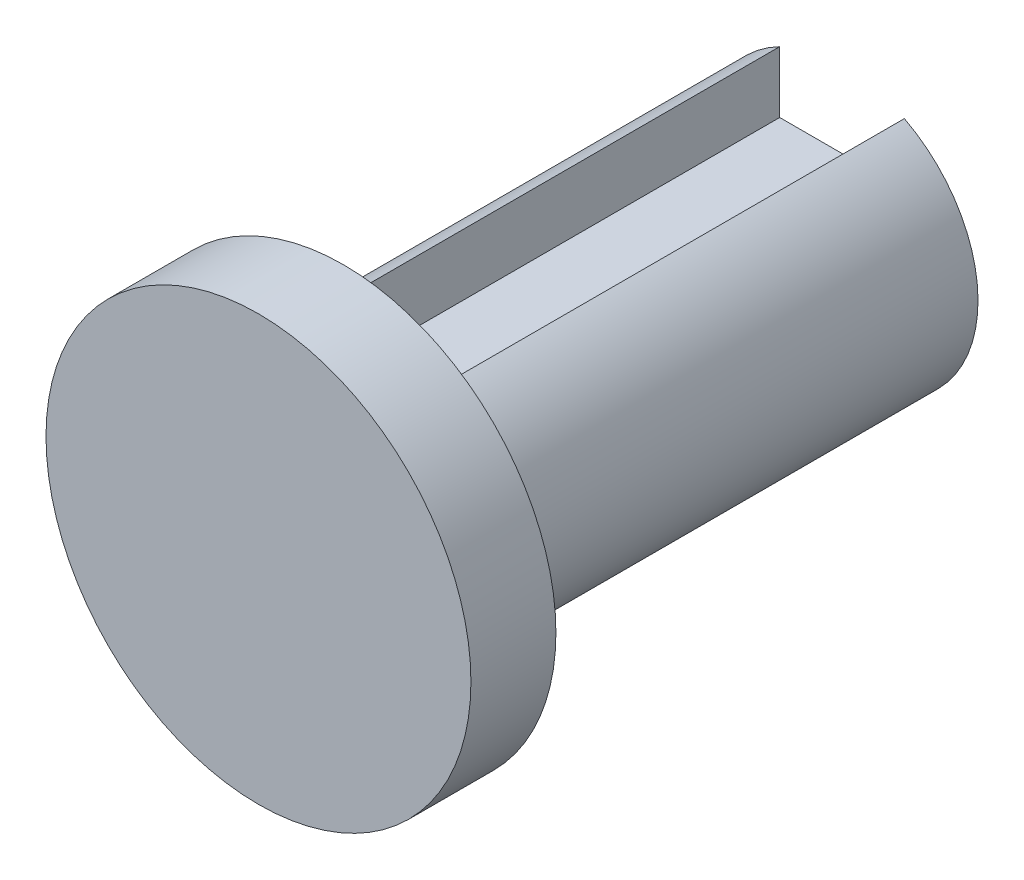
SolidWorks part; units mm, degrees
ref_plane "Front Plane" through (0, 0, 0) normal (0, 0, 1) x (1, 0, 0)
ref_plane "Top Plane" through (0, 0, 0) normal (0, 1, 0) x (1, 0, 0)
ref_plane "Right Plane" through (0, 0, 0) normal (1, 0, 0) x (0, 0, -1)
sketch "Sketch1" plane through (0, 0, 0) normal (0, 0, 1) x (1, 0, 0)
  line L0 (4.4, 4.2) -> (-4.4, 4.2)
  line L1 (4.4, 4.2) -> (4.4, 15)
  line L2 (4.4, 15) -> (-4.4, 15)
  line L3 (-4.4, 4.2) -> (-4.4, 15)
  line L4 (4.4, 4.2) -> (-4.4, 15) construction
  line L5 (4.4, 15) -> (-4.4, 4.2) construction
  circle A0 centre (0, 0) radius 9.6
  circle A1 centre (0, 0) radius 15
  point P2 (0, 9.6)
  dimension "D3" = 19.2
  dimension "D1" = 8.8
  dimension "D2" = 10.8
extrude "Boss-Extrude1" add sketch "Sketch1" along normal blind 6 contours A1
extrude "Boss-Extrude2" add sketch "Sketch1<3>" against normal blind 35.2 contours L3 A0 L1 L0 region at (0, -1.2221, 0)
sketch "Sketch1<3>" plane through (0, 0, 0) normal (0, 0, 1) x (1, 0, 0) same geometry as "Sketch1"
equation "\"shaftDiam\" = 20mm"
equation "\"keyW\" = 8mm"
equation "\"keyL\" = 10mm"
equation "\"clearance\" = .8mm"
equation "\"handleShaftLen\" = 60mm"
equation "\"panelH\" = 80mm"
equation "\"panelW\" = 110mm"
equation "\"D1@Sketch1\" = \"keyW\" + \"clearance\""
equation "\"D2@Sketch1\"= \"keyL\" + \"clearance\""
equation "\"D3@Sketch1\"=\"shaftDiam\"-\"clearance\""
equation "\"D1@Boss-Extrude1\"=\"handleShaftLen\"/10"
equation "\"D1@Boss-Extrude2\"=3*\"handleShaftLen\"/8+.5in"
